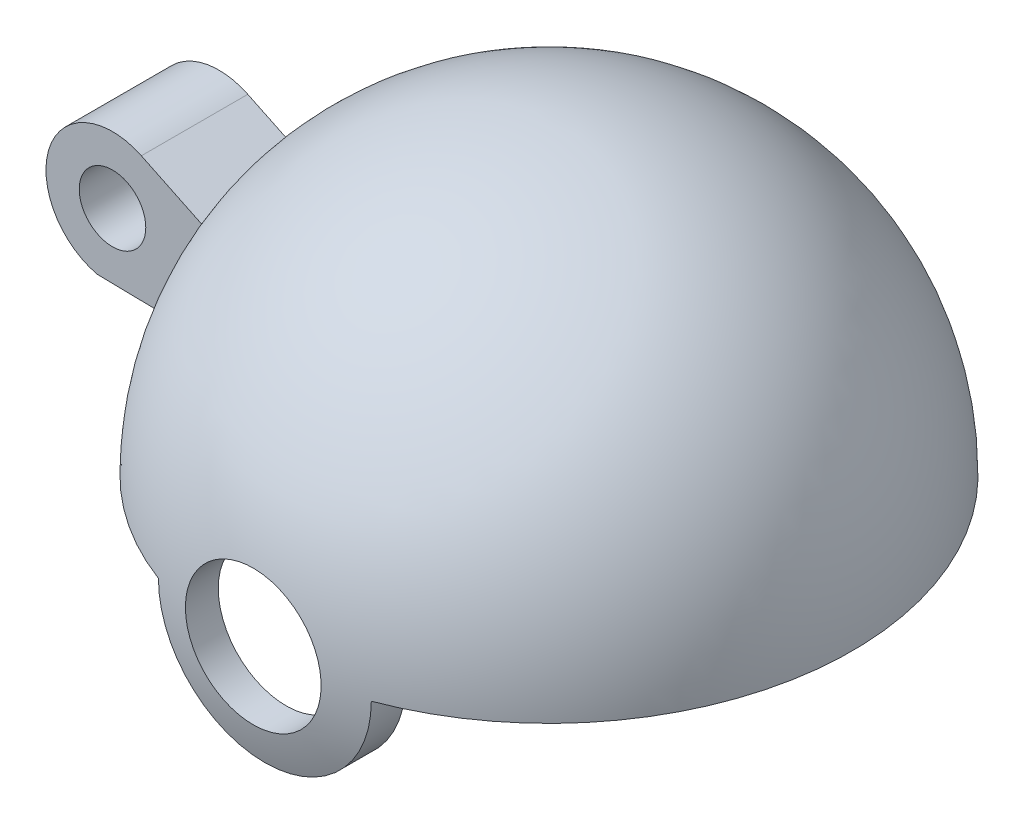
SolidWorks part; units mm, degrees
ref_plane "Front Plane" through (0, 0, 0) normal (0, 0, 1) x (1, 0, 0)
ref_plane "Top Plane" through (0, 0, 0) normal (0, 1, 0) x (1, 0, 0)
ref_plane "Right Plane" through (0, 0, 0) normal (1, 0, 0) x (0, 0, -1)
sketch "Sketch1" plane through (0, 0, 0) normal (0, 0, 1) x (1, 0, 0)
  line L1 (0, 0) -> (0, 14.478) construction
  line L2 (0, 14.478) -> (0, -14.478)
  arc A1 (0, 14.478) -> (0, -14.478) centre (0, 0) ccw
  arc A2 (0, 12.954) -> (0, -12.954) centre (0, 0) ccw
  dimension "D1" = 12.954
  dimension "D2" = 14.478
revolve "Revolve1" add sketch "Sketch1" angle 360 about L1 region at (-0.3237, 13.716, 0)
sketch "Sketch5" plane through (0, 0, 0) normal (0, 0, 1) x (1, 0, 0)
  line L0 (-13.7551, 4.5177) -> (-13.5099, 4.5177)
  line L1 (-14.478, 0) -> (-14.2328, 0)
  line L2 (-14.478, 0) -> (-19.029, 0.0877)
  line L3 (-14.478, 0) -> (-13.7551, 4.5177)
  line L4 (-16.9116, 6.0361) -> (-13.7551, 4.5177)
  line L5 (-13.5099, 4.5177) -> (-14.2328, 0)
  circle A3 centre (-18.288, 3.175) radius 3.175
  circle A4 centre (-18.288, 3.175) radius 1.5875
  circle A5 centre (0, 0) radius 14.478 construction
  point P3 (0, 0)
  point P5 (0, 0)
  point P10 (0, 0)
  dimension "D1" = 6.35
  dimension "D2" = 3.175
  dimension "D3" = 3.175
  dimension "D4" = 3.81
extrude "Boss-Extrude2" add sketch "Sketch5" against normal blind 5.08 from offset 2.54 contours A3 A4 | A3 L3 | L5 L0 L3 region at (-13.9939, 2.2588, 0) region at (-14.9919, 2.3943, 0) region at (-15.6757, 4.8172, 0)
sketch "Sketch7" plane through (0, 0, 0) normal (0, 0, 1) x (1, 0, 0)
  circle A0 centre (0, 0) radius 3.2385
  dimension "D1" = 6.477
extrude "Cut-Extrude2" cut sketch "Sketch7" against normal through all both and the other way through all
sketch "Sketch8" plane through (0, 0, 0) normal (0, 0, 1) x (1, 0, 0)
  line L0 (-14.478, 0) -> (-5.08, 0)
  line L1 (14.478, 0) -> (5.08, 0)
  arc A0 (-14.478, 0) -> (-13.7551, 4.5177) centre (0, 0) ccw construction
  arc A1 (5.08, 0) -> (-5.08, 0) centre (0, 0) cw
  dimension "D1" = 5.08
extrude "Cut-Extrude3" cut sketch "Sketch8" against normal through all both and the other way through all
